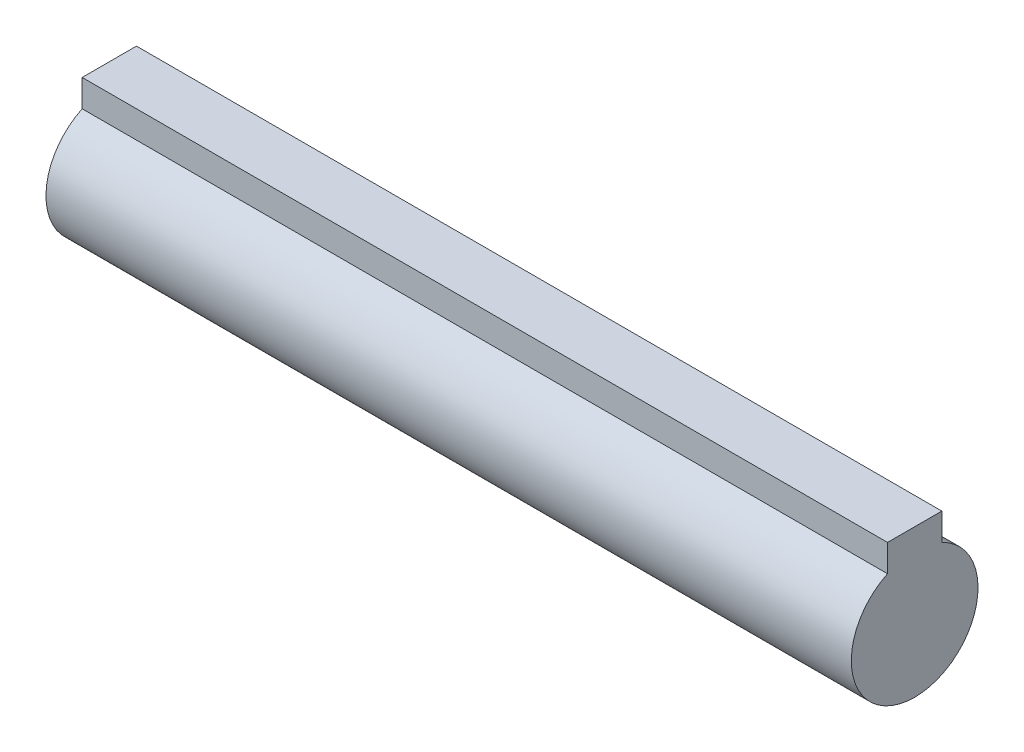
SolidWorks part; units mm, degrees
ref_plane "Plan de face" through (0, 0, 0) normal (0, 0, 1) x (1, 0, 0)
ref_plane "Plan de dessus" through (0, 0, 0) normal (0, 1, 0) x (1, 0, 0)
ref_plane "Plan de droite" through (0, 0, 0) normal (1, 0, 0) x (0, 0, -1)
sketch "Esquisse1" plane through (0, 0, 0) normal (1, 0, 0) x (0, 0, -1)
  line L1 (-1.5, 3.1623) -> (1.5, 3.1623) construction
  line L2 (-1.5, 3.1623) -> (-1.5, 4.6623)
  line L3 (-1.5, 4.6623) -> (1.5, 4.6623)
  line L4 (1.5, 3.1623) -> (1.5, 4.6623)
  circle A0 centre (0, 0) radius 3.5
  dimension "D1" = 7
  dimension "D2" = 3
  dimension "D3" = 1.5
extrude "Boss.-Extru.1" add sketch "Esquisse1" along normal blind 50 contours L1 A0 | A0 L4 L3 L2 | A0 region at (0, 4.0221, 0) region at (0, -0.0595, 0)
sketch "Esquisse4" plane through (50, 0, 0) normal (1, 0, 0) x (0, 0, -1)
  line L2 (-1.5, 3.1623) -> (-1.5, 4.6623)
  line L3 (-1.5, 4.6623) -> (1.5, 4.6623)
  line L4 (1.5, 3.1623) -> (1.5, 4.6623)
  arc A0 (-1.5, 3.1623) -> (1.5, 3.1623) centre (0, 0) cw
extrude "Enlèv. mat.-Extru.1" cut sketch "Esquisse4" against normal blind 6
ref_plane "Plan1" through (25, 0, 0) normal (1, 0, 0) x (0, 0, -1)
mirror "Symétrie1" about plane through (25, 0, 0) normal (1, 0, 0) of "Enlèv. mat.-Extru.1"
sketch "Esquisse5" plane through (0, 0, 0) normal (-1, 0, 0) x (0, 0, 1)
  circle A0 centre (0, 0) radius 3.5 construction
  circle A1 centre (0, 0) radius 3.5
extrude "Boss.-Extru.2" add sketch "Esquisse5" along normal blind 10
sketch "Esquisse6" plane through (0, 0, 0) normal (0, 0, 1) x (1, 0, 0)
  line L0 (-10, 0) -> (28.5, 0) construction
  line L1 (-10, 3.5) -> (-10, -3.5) construction
  line L2 (28.5, 0) -> (34.5, 0)
  line L4 (34.5, 8.2257) -> (52.6214, 8.2257)
  line L5 (34.5, 8.2257) -> (34.5, -8.5925)
  line L6 (34.5, -8.5925) -> (52.6214, -8.5925)
  line L7 (52.6214, 8.2257) -> (52.6214, -8.5925)
  dimension "D1" = 38.5
  dimension "D2" = 6
extrude "Enlèv. mat.-Extru.2" cut sketch "Esquisse6" against normal blind 10 and the other way blind 10 contours L7 L4 L5 L6 region at (43.5607, -0.1834, 0)
sketch "Esquisse7" plane through (34.5, 0, 0) normal (1, 0, 0) x (0, 0, -1)
  line L0 (-1.5, 3.1623) -> (-1.5, 4.6623)
  line L1 (-1.5, 3.1623) -> (-1.5, 4.6623) construction
  line L2 (-1.5, 4.6623) -> (1.5, 4.6623)
  line L3 (1.5, 4.6623) -> (1.5, 3.1623)
  arc A1 (1.5, 3.1623) -> (-1.5, 3.1623) centre (0, 0) ccw
  arc A2 (-1.5, 3.1623) -> (1.5, 3.1623) centre (0, 0) ccw construction
sketch "Esquisse8" plane through (6, 0, 0) normal (-1, 0, 0) x (0, 0, 1)
  line L3 (1.5, 3.1623) -> (1.5, 4.6623)
  line L4 (1.5, 4.6623) -> (-1.5, 4.6623)
  line L5 (-1.5, 4.6623) -> (-1.5, 3.1623)
  line L6 (1.5, 3.1623) -> (1.5, 4.6623)
  line L7 (1.5, 4.6623) -> (-1.5, 4.6623)
  line L8 (-1.5, 4.6623) -> (-1.5, 3.1623)
  arc A1 (1.5, 3.1623) -> (-1.5, 3.1623) centre (0, 0) ccw
  arc A2 (1.5, 3.1623) -> (-1.5, 3.1623) centre (0, 0) ccw
  dimension "D1" = 0
extrude "Boss.-Extru.3" add sketch "Esquisse8" along normal up to surface (16 mm away) up to face at (-10, 0, 3.5)
